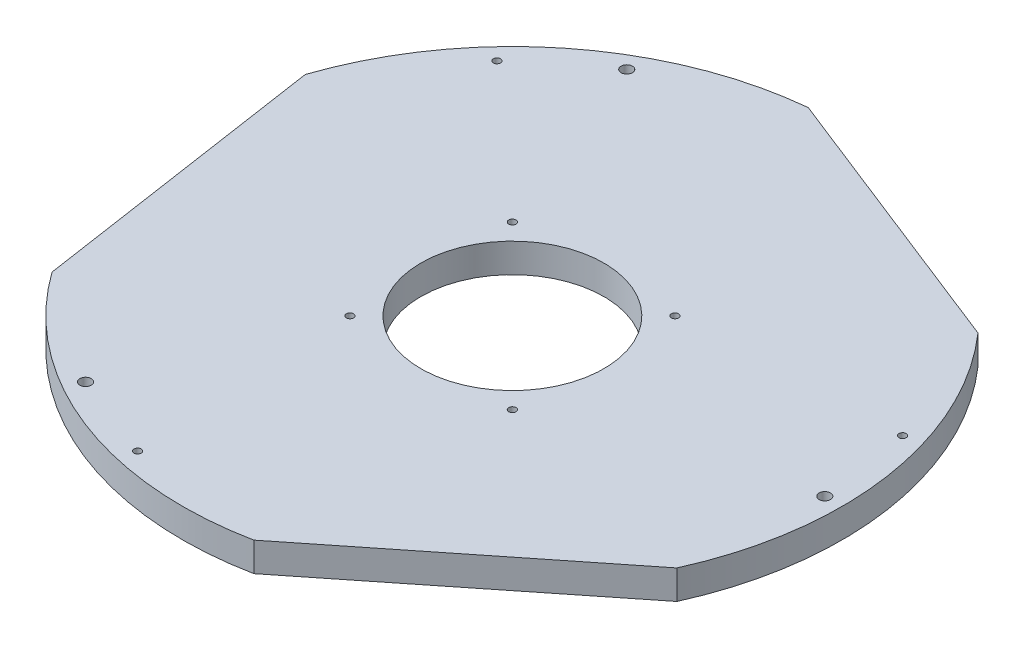
SolidWorks part; units mm, degrees
material "Oak"
ref_plane "Front Plane" through (0, 0, 0) normal (0, 0, 1) x (1, 0, 0)
ref_plane "Top Plane" through (0, 0, 0) normal (0, 1, 0) x (1, 0, 0)
ref_plane "Right Plane" through (0, 0, 0) normal (1, 0, 0) x (0, 0, -1)
sketch "Sketch1" plane through (0, 0, 0) normal (0, 0, 1) x (1, 0, 0)
  line L0 (0, -200000) -> (0, 218797.9879) construction
  line L1 (144.145, -22.3802) -> (144.145, -35.0802) construction
  line L2 (0, -22.3802) -> (144.145, -22.3802) construction
  line L3 (144.145, -35.0802) -> (0, -35.0802) construction
  line L4 (0, -200000) -> (0, 218797.9879) construction
  line L5 (144.145, -22.3802) -> (144.145, -35.0802)
  line L6 (0, -22.3802) -> (144.145, -22.3802)
  line L7 (144.145, -35.0802) -> (0, -35.0802)
  line L8 (0, -22.3802) -> (0, -35.0802)
revolve "Revolve1" add sketch "Sketch1" angle 360 about L4
hole_wizard "1/8 (0.125) Diameter Hole1" positions "Sketch2" profile "Sketch3" hole size "1/8" standard "ANSI Inch" end condition up to next
sketch "Sketch2" plane through (0, -22.3802, 0) normal (0, 1, 0) x (1, 0, 0)
  line L0 (0, 0) -> (136.525, 0) construction
  line L3 (0, 0) -> (-68.2625, -118.2341) construction
  line L6 (0, 0) -> (-68.2625, 118.2341) construction
  line L7 (-99.8481, 93.1098) -> (0, 0) construction
  line L9 (0, 0) -> (-30.7114, -133.0259) construction
  line L12 (0, 0) -> (130.5595, 39.916) construction
  line L14 (-35.5, -35.5) -> (35.5, -35.5) construction
  line L15 (-35.5, -35.5) -> (-35.5, 35.5) construction
  line L16 (-35.5, 35.5) -> (35.5, 35.5) construction
  line L17 (35.5, -35.5) -> (35.5, 35.5) construction
  line L18 (-35.5, 0) -> (0, 0) construction
  line L19 (0, 0) -> (0, -35.5) construction
  circle A0 centre (0, 0) radius 136.525
  point P0 (136.525, 0)
  point P2 (-68.2625, -118.2341)
  point P4 (-68.2625, 118.2341)
  point P32 (-99.8481, 93.1098)
  point P57 (130.5595, 39.916)
  point P60 (-30.7114, -133.0259)
  point P138 (-35.5, -35.5)
  point P141 (-35.5, 35.5)
  point P144 (35.5, 35.5)
  point P147 (35.5, -35.5)
  dimension "D3" = 17
  dimension "D1" = 120
  dimension "D2" = 120
  dimension "D4" = 120
  dimension "D5" = 120
  dimension "D6" = 71
sketch "Sketch3" plane through (136.525, -22.3802, 0) normal (1, 0, 0) x (0, 0, 1)
  line L0 (0, 0) -> (0, 12.7)
  line L1 (0, 12.7) -> (1.5875, 12.7)
  line L2 (1.5875, 12.7) -> (1.5875, 0)
  line L5 (1.5875, 0) -> (0, 0)
  line L11 (0, -6.35) -> (0, 107.95) construction
  dimension "Thru Hole Dia." = 3.175
  dimension "Thru Hole Depth" = 12.7
sketch "Sketch4" plane through (0, -22.3802, 0) normal (0, 1, 0) x (1, 0, 0)
  line L0 (253.7221, 37.919) -> (-94.0222, -238.6893)
  line L1 (-94.0222, -238.6893) -> (-159.6999, 200.7703)
  line L2 (-159.6999, 200.7703) -> (253.7221, 37.919)
  line L3 (253.7221, 37.919) -> (0, 0) construction
  line L4 (130.5595, 39.916) -> (136.525, 0) construction
  circle A0 centre (0, 0) radius 128.27 construction
  point P6 (133.5423, 19.958)
  dimension "D1" = 256.54
extrude "Cut-Extrude1" cut sketch "Sketch4" against normal through all flip side to cut
sketch "Sketch6" plane through (0, -22.3802, 0) normal (0, 1, 0) x (1, 0, 0)
  circle A0 centre (0, 0) radius 40
  dimension "D1" = 80
extrude "Cut-Extrude2" cut sketch "Sketch6" against normal through all
hole_wizard "M6x1.0 Tapped Hole1" positions "Sketch7" profile "Sketch8" tap size "M6x1.0" standard "ANSI Metric" end condition through all
sketch "Sketch7" plane through (0, -22.3802, 0) normal (0, 1, 0) x (1, 0, 0)
  point P0 (-68.2625, 118.2341)
  point P4 (136.525, 0)
  point P8 (-68.2625, -118.2341)
sketch "Sketch8" plane through (-68.2625, -22.3802, -118.2341) normal (1, 0, 0) x (0, 0, 1)
  line L0 (0, 0) -> (0, 12.7)
  line L1 (0, 12.7) -> (2.5, 12.7)
  line L2 (2.5, 12.7) -> (2.5, 0)
  line L5 (2.5, 0) -> (0, 0)
  line L11 (0, -6.35) -> (0, 107.95) construction
  dimension "Thru Tap Drill Dia." = 5
  dimension "Thru Tap Drill Depth" = 12.7
cosmetic thread "Hole Thread1" parameters "D2"=6
cosmetic thread "Hole Thread2" parameters "D2"=6
cosmetic thread "Hole Thread3" parameters "D2"=6
